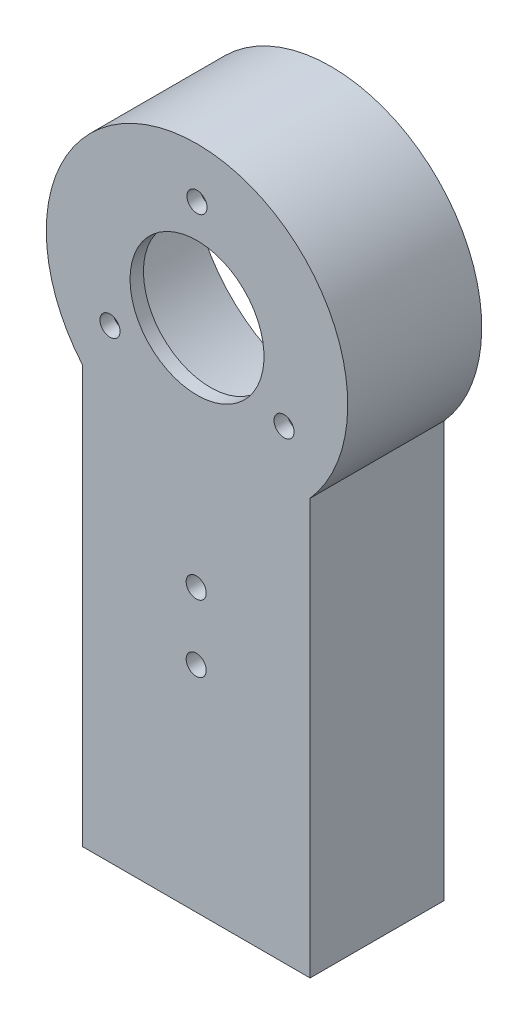
SolidWorks part; units mm, degrees
ref_plane "Front Plane" through (0, 0, 0) normal (0, 0, 1) x (1, 0, 0)
ref_plane "Top Plane" through (0, 0, 0) normal (0, 1, 0) x (1, 0, 0)
ref_plane "Right Plane" through (0, 0, 0) normal (1, 0, 0) x (0, 0, -1)
sketch "Sketch1" plane through (0, 0, 0) normal (0, 0, 1) x (1, 0, 0)
  line L1 (-17.1236, -14.5956) -> (-17.1236, -76.9)
  line L2 (16.8764, -14.8808) -> (16.8764, -76.9)
  line L3 (-17.1236, -76.9) -> (16.8764, -76.9)
  circle A0 centre (0, 0) radius 22.5
  arc A1 (-17.1236, -14.5956) -> (16.8764, -14.8808) centre (0, 0) ccw
  circle A2 centre (-0.1236, -44.9) radius 1.5
  circle A3 centre (-0.1236, -34.9) radius 1.5
  dimension "D1" = 45
  dimension "D4" = 3
  dimension "D5" = 3
  dimension "D6" = 32
  dimension "D7" = 42
  dimension "D2" = 76.9
  dimension "D3" = 34
extrude "Boss-Extrude1" add sketch "Sketch1" along normal blind 20 contours A0 L1 L3 L2 | A0 L1 region at (-0.1354, -48.5303, 0) region at (0, 0, 0)
sketch "Sketch2" plane through (0, 0, 0) normal (0, 0, -1) x (-1, 0, 0)
  circle A0 centre (0, 0) radius 10
  dimension "D1" = 20
extrude "Cut-Extrude1" cut sketch "Sketch2" against normal blind 20
sketch "Sketch3" plane through (0, 0, 0) normal (0, 0, -1) x (-1, 0, 0)
  circle A0 centre (0, 15) radius 1.5
  circle A1 centre (12.9904, -7.5) radius 1.5
  circle A2 centre (-12.9904, -7.5) radius 1.5
  point P10 (0, 0)
  dimension "D1" = 3
  dimension "D2" = 15
  dimension "D3" = 3
extrude "Cut-Extrude2" cut sketch "Sketch3" against normal blind 20
sketch "Sketch4" plane through (0, 0, 0) normal (0, 0, -1) x (-1, 0, 0)
  circle A0 centre (0, 0) radius 21
  dimension "D1" = 42
extrude "Cut-Extrude3" cut sketch "Sketch4" against normal blind 18
sketch "Sketch5" plane through (0, -76.9, 0) normal (0, -1, 0) x (1, 0, 0)
  line L0 (-17.1236, 20) -> (-17.1236, 0) construction
  line L1 (16.8764, 20) -> (16.8764, 0) construction
  circle A0 centre (-7.1236, 10) radius 1.5
  circle A1 centre (6.8764, 10) radius 1.5
  dimension "D1" = 3
  dimension "D2" = 3
  dimension "D3" = 10
  dimension "D4" = 10
extrude "Cut-Extrude4" cut sketch "Sketch5" against normal blind 15
